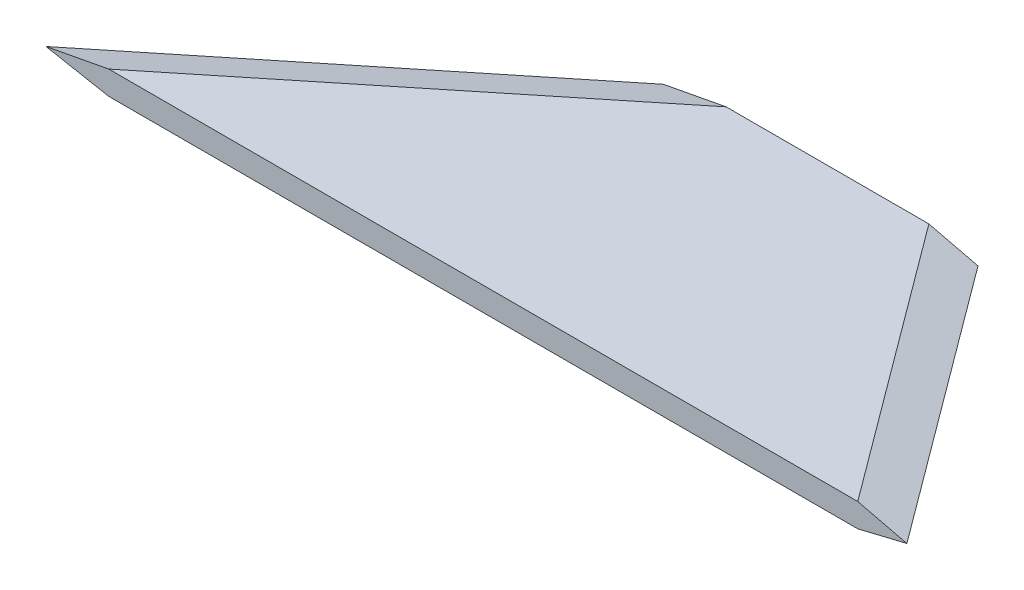
SolidWorks part; units mm, degrees
ref_plane "Front Plane" through (0, 0, 0) normal (0, 0, 1) x (1, 0, 0)
ref_plane "Top Plane" through (0, 0, 0) normal (0, 1, 0) x (1, 0, 0)
ref_plane "Right Plane" through (0, 0, 0) normal (1, 0, 0) x (0, 0, -1)
sketch "Sketch1" plane through (0, 0, 0) normal (0, 1, 0) x (1, 0, 0)
  line L0 (0, 0) -> (203.2, 0)
  line L1 (203.2, 0) -> (157.48, 61.595)
  line L2 (157.48, 61.595) -> (76.2, 61.595)
  line L3 (76.2, 61.595) -> (0, 0)
  dimension "D1" = 203.2
  dimension "D2" = 81.28
  dimension "D3" = 61.595
  dimension "D4" = 76.2
extrude "Boss-Extrude1" add sketch "Sketch1" along normal blind 5.2832
chamfer "Chamfer1" distance 3.81 distance2 12.7 1 edges at (180.34, 5.2832, -30.7975) first distance on face at (180.34, 2.6416, -30.7975)
chamfer "Chamfer2" distance 12.7 distance2 3.81 1 edges at (180.34, 0, -30.7975) first distance on face at (109.22, 0, -30.7975)
chamfer "Chamfer3" distance 3.81 distance2 12.7 1 edges at (38.1, 5.2832, -30.7975) first distance on face at (38.1, 2.6416, -30.7975)
chamfer "Chamfer4" distance 12.7 distance2 3.81 1 edges at (38.1, 0, -30.7975) first distance on face at (101.3119, 0, -30.7975)
